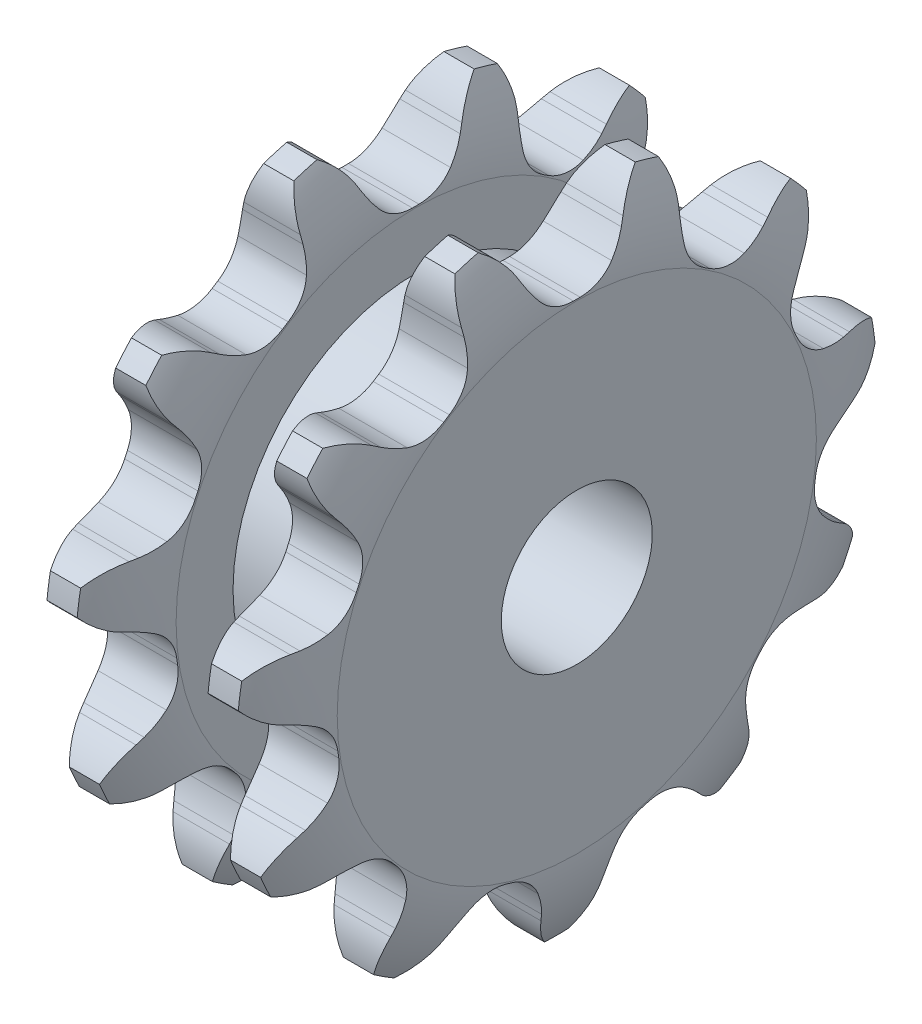
SolidWorks part; units mm, degrees
ref_plane "Plane1" through (0, 0, 0) normal (0, 0, 1) x (1, 0, 0)
ref_plane "Plane2" through (0, 0, 0) normal (0, 1, 0) x (1, 0, 0)
ref_plane "Plane3" through (0, 0, 0) normal (1, 0, 0) x (0, 0, -1)
sketch "Clipboard" plane through (0, 0, 0) normal (0, 1, 0) x (1, 0, 0)
  line L0 (0, 0) -> (6.2333, -1.2116)
  line L1 (-15, 0) -> (100, 0) construction
  line L2 (0, 0) -> (-0.5301, 0.5991)
  line L3 (0, 0) -> (-2.9891, 1.1425)
  line L4 (0, 0) -> (3.043, 0.5915)
  line L5 (0, 0) -> (-89.0105, -33.1983)
  line L6 (0, 0) -> (-7.6265, -5.1456)
  line L7 (-0.5301, 0.5991) -> (92.0355, 21.9696)
  line L8 (-76.2, 38.1) -> (-75.2, 38.1)
  line L9 (-73.2358, 39.4872) -> (-73.0836, 39.4947)
  line L10 (-73.0533, 76.1892) -> (-66.6533, 76.1892)
  circle A0 centre (0, 0) radius 1.651
  circle A1 centre (0, 0) radius 4
  circle A2 centre (0, 0) radius 4
  dimension "Num_teeth" = 11
  dimension "Thickness" = 9.2
sketch "BasProSke" plane through (0, 0, 0) normal (0, 1, 0) x (1, 0, 0)
  line L0 (-10, 0) -> (60, 0) construction
  line L1 (0, 0) -> (0, 9.5181)
  line L2 (0, 0) -> (9.2, 0)
  line L3 (9.2, 0) -> (9.2, 9.5181)
  line L4 (8.4, 12.7181) -> (0.8, 12.7181)
  arc A0 (0, 9.5181) -> (0.8, 12.7181) centre (6.8, 9.5181) cw
  arc A1 (9.2, 9.5181) -> (8.4, 12.7181) centre (2.4, 9.5181) ccw
  dimension "D1" = 6.8
  dimension "Thickness" = 9.2
  dimension "Diameter" = 25.4361
  dimension "H1" = 3.2
  dimension "G1" = 0.8
revolve "Base-Revolve" add sketch "BasProSke" angle 360 about L0
sketch "GrvSke" plane through (0, 0, 0) normal (0, 1, 0) x (1, 0, 0)
  line L0 (2.8, 9.5181) -> (2.8, 7.2571)
  line L1 (2.8, 7.2571) -> (6.4, 7.2571)
  line L2 (6.4, 7.2571) -> (6.4, 9.5181)
  line L3 (2, 12.7181) -> (7.2, 12.7181)
  line L4 (4.6, 0) -> (4.6, 52.07) construction
  line L5 (-10, 0) -> (60, 0) construction
  line L6 (0, 0) -> (35.56, 0) construction
  arc A0 (6.4, 9.5181) -> (7.2, 12.7181) centre (13.2, 9.5181) cw
  arc A1 (2.8, 9.5181) -> (2, 12.7181) centre (-4, 9.5181) ccw
  dimension "Diameter" = 25.4361
  dimension "H1" = 3.2
  dimension "G1" = 0.8
revolve "Groove" cut sketch "GrvSke" angle 360 about L6
pattern_linear "Grooves" [suppressed]
sketch "TooCutSke" plane through (0, 0, 0) normal (1, 0, 0) x (0, 0, -1)
  line L0 (1.9692, 10.9762) -> (2.1109, 11.2478)
  line L1 (0, 0) -> (0, 107) construction
  line L2 (0.2483, 11.2688) -> (-2.0258, 11.2688) construction
  line L4 (0.1322, 12.3974) -> (0.1322, 8.6148) construction
  line L5 (0.1322, 9.5714) -> (-0.1322, 9.5714)
  line L6 (-1.9692, 10.9762) -> (-2.1109, 11.2478)
  arc A0 (1.4237, 10.1675) -> (1.9692, 10.9762) centre (-1.8779, 12.9828) ccw
  arc A1 (1.4237, 10.1675) -> (0.1322, 9.5714) centre (0.1322, 11.2688) cw
  arc A2 (2.1109, 11.2478) -> (4.5677, 12.7373) centre (4.5677, 9.9664) cw
  arc A3 (-0.1322, 9.5714) -> (-1.4237, 10.1675) centre (-0.1322, 11.2688) cw
  arc A4 (-1.4237, 10.1675) -> (-1.9692, 10.9762) centre (1.8779, 12.9828) cw
  arc A5 (-2.1109, 11.2478) -> (-4.5677, 12.7373) centre (-4.5677, 9.9664) ccw
  arc A6 (4.5677, 12.7373) -> (-4.5677, 12.7373) centre (0, 0) ccw
  dimension "Pitch_radius" = 11.2696
  dimension "V" = 1.3024
  dimension "D1" = 1.8779
extrude "ToothCut" cut sketch "TooCutSke" along normal through all
pattern_circular "TeethCuts" count 11 every 32.727 about axis through (-10, 0, 0) along (1, 0, 0) of "ToothCut"
sketch "HubNeaOneSke" plane through (0, 0, 0) normal (-1, 0, 0) x (0, 0, 1)
  circle A0 centre (0, 0) radius 4
  dimension "Diameter" = 8
extrude "HubNearOne" [suppressed] add sketch "HubNeaOneSke" along normal blind 85.8005
sketch "HubNeaBotSke" plane through (0, 0, 0) normal (-1, 0, 0) x (0, 0, 1)
  circle A0 centre (0, 0) radius 4
  dimension "Diameter" = 8
extrude "HubNearBoth" [suppressed] add sketch "HubNeaBotSke" along normal blind 42.9002
ref_plane "FarPln" through (9.2, 0, 0) normal (1, 0, 0) x (0, 0, -1)
sketch "HubFarSke" plane through (9.2, 0, 0) normal (1, 0, 0) x (0, 0, -1)
  circle A0 centre (0, 0) radius 4
  dimension "Diameter" = 8
extrude "HubFar" [suppressed] add sketch "HubFarSke" along normal blind 42.9002
sketch "BorSke" plane through (0, 0, 0) normal (1, 0, 0) x (0, 0, -1)
  circle A0 centre (0, 0) radius 3
  dimension "Diameter" = 6
extrude "Bore" cut sketch "BorSke" along normal mid plane 190.001
sketch "KeySke" plane through (0, 0, 0) normal (1, 0, 0) x (0, 0, -1)
  line L0 (-1, 0) -> (-1, 4)
  line L1 (-1, 4) -> (1, 4)
  line L2 (1, 4) -> (1, 0)
  line L3 (0, 0) -> (0, 34) construction
  line L4 (-1, 0) -> (1, 0)
  dimension "Offset" = 4
  dimension "Width" = 2
extrude "Keyway" [suppressed] cut sketch "KeySke" along normal mid plane 190.001
pattern_circular "Keyway2" [suppressed] count 2 every 90 about axis through (-10, 0, 0) along (1, 0, 0) reverse direction yes
equation "' \"Pitch@Clipboard\" = 6.35"
equation "' \"Num_strands@Clipboard\" = 2"
equation "' \"Num_teeth@Clipboard\" = 11"
equation "' \"Hub_dia@Clipboard\" = 8"
equation "' \"Overall_len@Clipboard\" = 95"
equation "' \"Diameter@BorSke\" = 6"
equation "' \"T_dim@Clipboard\" = 1"
equation "' \"Width@KeySke\" = 2"
equation "' \"Dr@Clipboard\" = 3.302"
equation "' \"Face_width@Clipboard\" = 2.8"
equation "' \"Chamfer_dep@Clipboard\" = 3.2"
equation "' \"Chamfer_wid@Clipboard\" = 0.8"
equation "' \"Transv_pitch@Clipboard\" = 6.4"
equation "' \"Show_teeth@Clipboard\" = 11"
equation "\"Num_teeth@Clipboard\" = int( \"Num_teeth@Clipboard\" )"
equation "\"Num_teeth@Clipboard\" = ((sgn( \"Num_teeth@Clipboard\" - 5.0)+1)*( \"Num_teeth@Clipboard\" - 5.0))/2 +5.0"
equation "\"Num_teeth@Clipboard\" = ((sgn( \"Num_teeth@Clipboard\" - 200.0)-1)*( \"Num_teeth@Clipboard\" - 200.0))/-2 +200.0"
equation "\"MHD@Clipboard\" = \"Pitch@Clipboard\" * (1.0 / tan(3.14159265 / \"Num_teeth@Clipboard\" ) - 1.0) - 0.762"
equation "\"Thickness@Clipboard\"  = \"Face_width@Clipboard\" + (\"Num_strands@Clipboard\" - 1) * \"Transv_pitch@Clipboard\""
equation "\"OAL@Clipboard\" = \"Thickness@Clipboard\""
equation "\"MHD@Clipboard\" = ((sgn( \"MHD@Clipboard\" - \"Hub_dia@Clipboard\" )-1)*( \"MHD@Clipboard\" - \"Hub_dia@Clipboard\" ))/-2+ \"Hub_dia@Clipboard\""
equation "\"OAL@Clipboard\" = ((sgn( \"OAL@Clipboard\" - \"Overall_len@Clipboard\" )+1)*( \"OAL@Clipboard\" - \"Overall_len@Clipboard\" ))/2 + \"Overall_len@Clipboard\" + 0.0005"
equation "\"Num_teeth@TeethCuts\" = int( \"Show_teeth@Clipboard\" ) + 1"
equation "\"Num_teeth@TeethCuts\" = ((sgn( \"Num_teeth@TeethCuts\" - \"Num_teeth@Clipboard\" )-1)*( \"Num_teeth@TeethCuts\" - \"Num_teeth@Clipboard\" ))/-2+ \"Num_teeth@Clipboard\""
equation "\"Num_teeth@TeethCuts\" = ((sgn( \"Num_teeth@TeethCuts\" - 2.0)+1)*( \"Num_teeth@TeethCuts\" - 2.0))/2 +2.0"
equation "\"Angle@TeethCuts\" = 360.0 / \"Num_teeth@Clipboard\""
equation "\"Pitch_radius@TooCutSke\" = ( \"Pitch@Clipboard\" / 2.0) / sin(3.14159265 / \"Num_teeth@Clipboard\" )  'ma"
equation "\"Half_U@TooCutSke\" = 0.5 * (0.07 * (\"Pitch@Clipboard\" - \"Dr@Clipboard\") + 0.051)"
equation "\"R@TooCutSke\"  = \"Dr@Clipboard\" * 0.5025 + 0.0381"
equation "\"A@TooCutSke\" = 35.0 + (60.0 / \"Num_teeth@Clipboard\")"
equation "\"E@TooCutSke\"  = \"Dr@Clipboard\" * 1.3025 + 0.0381"
equation "\"B@TooCutSke\"  = 18.0 - (56.0 / \"Num_teeth@Clipboard\" )"
equation "\"W@TooCutSke\" = 1.4 * \"Dr@Clipboard\" * cos(3.14159265 / \"Num_teeth@Clipboard\" ) + \"Half_U@TooCutSke\""
equation "\"V@TooCutSke\" = 1.4 * \"Dr@Clipboard\" * sin(3.14159265 / \"Num_teeth@Clipboard\" )"
equation "\"Diameter@BasProSke\" = 2.0 * ( (0.3 * \"Pitch@Clipboard\" ) +  \"Pitch@Clipboard\" / 2.0 / tan(3.14159265 / \"Num_teeth@Clipboard\" ))"
equation "\"Thickness@BasProSke\"  = \"Thickness@Clipboard\""
equation "\"G1@BasProSke\" =  \"Chamfer_wid@Clipboard\""
equation "\"G2@BasProSke\" =  \"Chamfer_wid@Clipboard\""
equation "\"H1@BasProSke\" =  \"Chamfer_dep@Clipboard\""
equation "\"H2@BasProSke\" =  \"Chamfer_dep@Clipboard\""
equation "\"Diameter@GrvSke\" = \"Diameter@BasProSke\""
equation "\"G1@GrvSke\" = \"Chamfer_wid@Clipboard\""
equation "\"H1@GrvSke\" = \"Chamfer_dep@Clipboard\""
equation "\"Grv_diam@GrvSke\" =  \"Pitch@Clipboard\" * (1.0 / tan(3.14159265 / \"Num_teeth@Clipboard\" ) - 1.0) - 0.762"
equation "\"Grv_width@GrvSke\" =  \"Transv_pitch@Clipboard\" - \"Face_width@Clipboard\""
equation "\"Offset@GrvSke\" = \"Grv_width@GrvSke\" / 2.0 + \"Face_width@Clipboard\""
equation "\"Offset@Grooves\" = \"Transv_pitch@Clipboard\""
equation "\"Num_grvs@Grooves\" = \"Num_strands@Clipboard\""
equation "\"Num_grvs@Grooves\" = \"Num_grvs@Grooves\" - 1 * sgn( \"Num_grvs@Grooves\" -1)"
equation "\"Diameter@HubNeaOneSke\" = \"MHD@Clipboard\""
equation "\"Length@HubNearOne\" = \"OAL@Clipboard\" - \"Thickness@BasProSke\""
equation "\"Diameter@HubNeaBotSke\" = \"MHD@Clipboard\""
equation "\"Length@HubNearBoth\" = ( \"OAL@Clipboard\" - \"Thickness@BasProSke\" ) / 2.0"
equation "\"Thickness@FarPln\" = \"Thickness@BasProSke\""
equation "\"Diameter@HubFarSke\" = \"MHD@Clipboard\""
equation "\"Length@HubFar\" = ( \"OAL@Clipboard\" - \"Thickness@BasProSke\" ) / 2.0"
equation "\"D1@Bore\" = \"OAL@Clipboard\" * 2.0"
equation "\"D1@Keyway\" = \"OAL@Clipboard\" * 2.0"
equation "\"Offset@KeySke\" = \"T_dim@Clipboard\" + \"Diameter@BorSke\" / 2.0"
